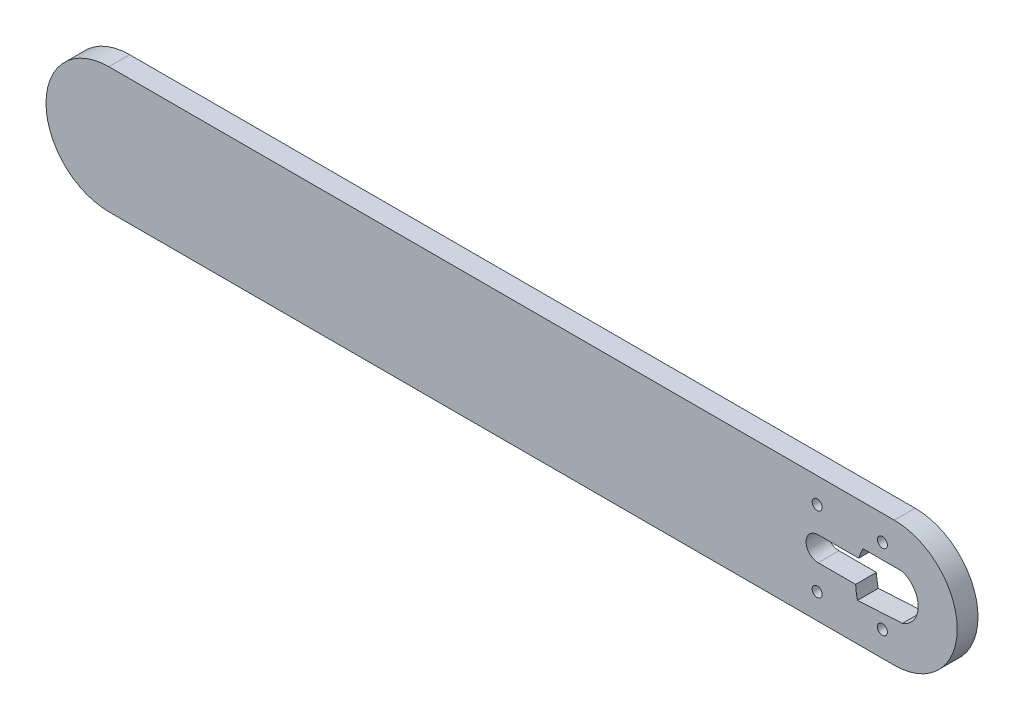
SolidWorks part; units mm, degrees
ref_plane "Front Plane" through (0, 0, 0) normal (0, 0, 1) x (1, 0, 0)
ref_plane "Top Plane" through (0, 0, 0) normal (0, 1, 0) x (1, 0, 0)
ref_plane "Right Plane" through (0, 0, 0) normal (1, 0, 0) x (0, 0, -1)
sketch "Sketch1" plane through (0, 0, 0) normal (0, 0, 1) x (1, 0, 0)
  line L0 (-53.15, -20.3675) -> (-303.15, -20.3675)
  line L1 (-303.15, 19.6325) -> (-53.15, 19.6325)
  arc A0 (-303.15, -20.3675) -> (-303.15, 19.6325) centre (-303.15, -0.3675) cw
  arc A1 (-53.15, 19.6325) -> (-53.15, -20.3675) centre (-53.15, -0.3675) cw
  dimension "D1" = 20
  dimension "D2" = 250
extrude "Boss-Extrude1" add sketch "Sketch1" along normal blind 6.62
sketch "Sketch2" plane through (0, 0, 0) normal (0, 0, -1) x (-1, 0, 0)
  line L0 (53.15, -0.3675) -> (43.5345, -3.1139) construction
  line L1 (53.15, -0.3675) -> (77.4, -0.3675) construction
  line L2 (50.5729, 6.7822) -> (63.15, 6.7822)
  line L3 (50.5729, -7.5172) -> (64.8779, -8.3255)
  line L4 (53.15, 19.6325) -> (303.15, 19.6325) construction
  line L5 (77.4, 3.4825) -> (64.4913, 3.4825)
  line L6 (77.4, -4.2175) -> (65.4772, -4.2175)
  line L7 (45.55, -0.3675) -> (45.55, 4.4582) construction
  line L8 (81.25, -0.3675) -> (81.25, 3.7385) construction
  arc A0 (50.5729, 6.7822) -> (50.5729, -7.5172) centre (53.15, -0.3675) ccw
  arc A1 (64.8779, -8.3255) -> (65.4772, -4.2175) centre (43.5345, -3.1139) ccw
  arc A2 (77.4, -4.2175) -> (77.4, 3.4825) centre (77.4, -0.3675) ccw
  arc A3 (64.4913, 3.4825) -> (63.15, 6.7822) centre (43.5345, -3.1139) ccw
  point P5 (58.15, -0.3675)
  dimension "D2" = 7.6
  dimension "D3" = 7.7
  dimension "D1" = 10
  dimension "D4" = 35.7
extrude "Cut-Extrude1" cut sketch "Sketch2" against normal up to next
sketch "Sketch3" plane through (0, 0, 0) normal (0, 0, -1) x (-1, 0, 0)
  circle A0 centre (77.7155, -12.3675) radius 1.6
  circle A1 centre (77.7155, 11.6325) radius 1.6
  circle A2 centre (56.9655, 11.6325) radius 1.6
  circle A3 centre (56.9655, -12.3675) radius 1.6
extrude "Cut-Extrude2" cut sketch "Sketch3" against normal up to next
sketch "Sketch4" plane through (0, 0, 0) normal (0, 0, -1) x (-1, 0, 0)
  circle A0 centre (56.9655, 11.6325) radius 2.75
  circle A1 centre (77.7155, 11.6325) radius 2.75
  circle A2 centre (77.7155, -12.3675) radius 2.75
  circle A3 centre (56.9655, -12.3675) radius 2.75
  dimension "D1" = 5.5
extrude "Cut-Extrude3" cut sketch "Sketch4" against normal blind 3.2
